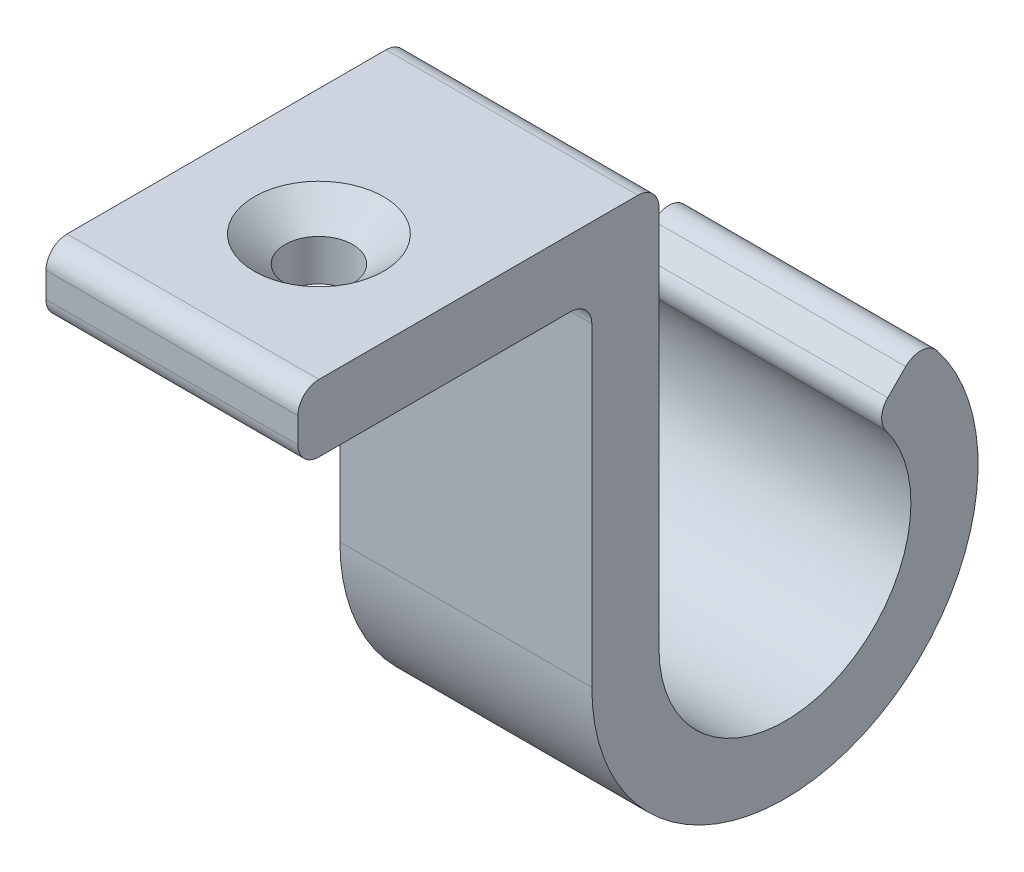
SolidWorks part; units mm, degrees
ref_plane "Front Plane" through (0, 0, 0) normal (0, 0, 1) x (1, 0, 0)
ref_plane "Top Plane" through (0, 0, 0) normal (0, 1, 0) x (1, 0, 0)
ref_plane "Right Plane" through (0, 0, 0) normal (1, 0, 0) x (0, 0, -1)
sketch "Sketch1" plane through (0, 0, 0) normal (1, 0, 0) x (0, 0, -1)
  line L0 (0, 0) -> (13.6525, -2.54) construction
  line L1 (-13.6525, -2.54) -> (8.5725, -2.54)
  line L2 (-13.6525, -2.54) -> (-13.6525, 2.54)
  line L3 (-13.6525, 2.54) -> (13.6525, 2.54)
  line L4 (13.6525, -27.94) -> (13.6525, 2.54)
  line L5 (-13.6525, -2.54) -> (13.6525, 2.54) construction
  line L6 (-13.6525, 2.54) -> (0, 0) construction
  line L7 (8.5725, -27.94) -> (13.6525, -27.94) construction
  line L8 (8.5725, -27.94) -> (8.5725, -2.54)
  line L9 (8.5725, -2.54) -> (13.6525, -2.54) construction
  line L11 (8.5725, -27.94) -> (13.6525, -2.54) construction
  line L12 (8.5725, -2.54) -> (13.6525, -27.94) construction
  line L13 (8.5725, -2.54) -> (13.6525, -2.54) construction
  line L14 (29.9127, -21.2048) -> (33.5048, -17.6127)
  arc A0 (8.5725, -27.94) -> (33.5048, -17.6127) centre (23.1775, -27.94) ccw
  arc A1 (13.6525, -27.94) -> (29.9127, -21.2048) centre (23.1775, -27.94) ccw
  point P0 (0, 0)
  point P6 (11.1125, -15.24)
  point P14 (43.2701, -22.5693)
  point P15 (37.6762, -24.8797)
  point P16 (0, 0)
  dimension "D4" = 9.525
  dimension "D1" = 5.08
  dimension "D2" = 22.225
  dimension "D3" = 25.4
  dimension "D5" = 45
extrude "Boss-Extrude1" add sketch "Sketch1" along normal mid plane 19.05
fillet "Fillet1" radius 1.5875 6 edges at (0, 2.54, 13.6525) (0, -2.54, 13.6525) (0, -2.54, -8.5725) (0, 2.54, -13.6525) (0, -17.6127, -33.5048) (0, -21.2048, -29.9127)
sketch "Sketch2" plane through (0, 2.54, 0) normal (0, 1, 0) x (1, 0, 0)
  line L0 (-9.525, 6.985) -> (9.525, -12.065) construction
  point P4 (0, -2.54)
hole_wizard "CSK for #10 Flat Head Machine Screw (100)1" positions "3DSketch1" profile "Sketch3" countersink size "#10" standard "ANSI Inch" end condition through all
sketch3d "3DSketch1"
  point P0 (0, 2.54, 2.54)
sketch "Sketch3" plane through (0, 2.54, 2.54) normal (1, 0, 0) x (0, 0, 1)
  line L0 (0, 0) -> (0, 45.085)
  line L1 (0, 45.085) -> (2.5527, 45.085)
  line L2 (2.5527, 45.085) -> (2.5527, 1.9608)
  line L3 (2.5527, 1.9608) -> (4.8895, 0)
  line L5 (4.8895, 0) -> (0, 0)
  line L6 (-2.5527, 1.9608) -> (-4.8895, 0) construction
  line L11 (0, -6.35) -> (0, 107.95) construction
  dimension "Thru Hole Dia." = 5.1054
  dimension "Thru Hole Depth" = 45.085
  dimension "Near C'Sink Dia." = 9.779
  dimension "Near C'Sink Angle" = 100
